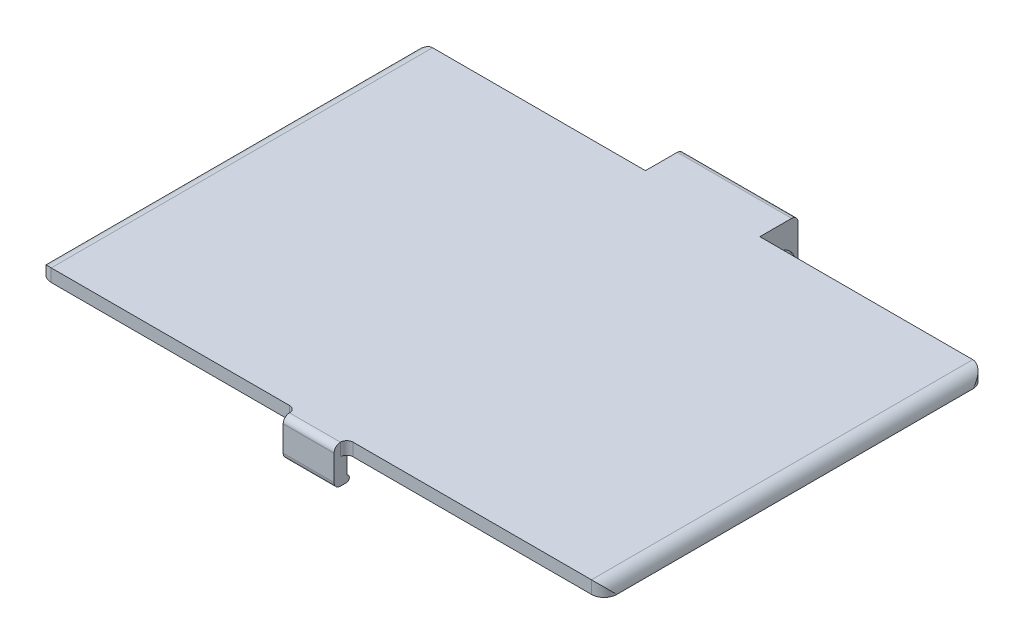
SolidWorks part; units mm, degrees
ref_plane "Přední rovina" through (0, 0, 0) normal (0, 0, 1) x (1, 0, 0)
ref_plane "Horní rovina" through (0, 0, 0) normal (0, 1, 0) x (1, 0, 0)
ref_plane "Pravá rovina" through (0, 0, 0) normal (1, 0, 0) x (0, 0, -1)
sketch "Sketch1" plane through (0, 0, 0) normal (0, 1, 0) x (1, 0, 0)
  line L0 (0, 30) -> (89, 30) construction
  line L1 (0, 0) -> (89, 0)
  line L2 (0, 0) -> (0, 60)
  line L3 (0, 60) -> (89, 60)
  line L4 (89, 0) -> (89, 60)
  line L5 (40.5, 0) -> (48.5, 0)
  line L6 (40.5, 0) -> (40.5, -1)
  line L7 (40.5, -1) -> (48.5, -1)
  line L8 (48.5, 0) -> (48.5, -1)
  line L9 (40.5, 61) -> (48.5, 61)
  line L10 (48.5, 60) -> (48.5, 61)
  line L11 (40.5, 60) -> (48.5, 60)
  line L12 (40.5, 60) -> (40.5, 61)
  point P9 (44.5, 0)
  point P10 (44.5, 0)
  dimension "D1" = 60
  dimension "D2" = 89
  dimension "D3" = 1
  dimension "D4" = 8
extrude "Boss-Extrude1" add sketch "Sketch1" along normal blind 2 contours L2 L0 L4 L3 | L0 L2 L1 L4 | L2 L1 L4 L3 region at (44.5, 0, -45) region at (44.5, 0, -15)
fillet "Fillet6" radius 2 4 edges at (0, 1, 0) (0, 1, -60) (89, 1, -60) (89, 1, 0)
fillet "Fillet8" radius 2 2 edges at (89, 2, -30) (0, 2, -30) tangent propagation no
sketch "Sketch3" plane through (0, 0, -60) normal (0, 0, -1) x (-1, 0, 0)
  line L0 (-44.5, 2) -> (-44.5, 0) construction
  line L1 (-2, 2) -> (-87, 2) construction
  line L2 (-2, 0) -> (-87, 0) construction
  line L4 (-53.5, 2) -> (-35.5, 2)
  line L5 (-53.5, 2) -> (-53.5, -8)
  line L6 (-53.5, -8) -> (-35.5, -8)
  line L7 (-35.5, 2) -> (-35.5, -8)
  line L8 (-51.5, -8) -> (-37.5, -8)
  line L9 (-51.5, -8) -> (-51.5, 0)
  line L10 (-51.5, 0) -> (-37.5, 0)
  line L11 (-37.5, -8) -> (-37.5, 0)
  point P10 (-44.5, 2)
  point P16 (-44.5, 0)
  line M10 (-87, 0) -> (-2, 0)
  line M12 (-2, 2) -> (-87, 2)
  dimension "D1" = 8
  dimension "D2" = 18
  dimension "D3" = 2
extrude "Boss-Extrude2" add sketch "Sketch3" along normal blind 6 contours L6 L9 L5 M10 | L0 L4 L5 M10 | L0 L10 L7 M12 M10 | L11 L6 L7 M10 region at (40, 1, -60) region at (49, 1, -60) region at (52.5, -4, -60) region at (36.5, -4, -60)
ref_plane "Plane2" through (0, 0, -63) normal (0, 0, 1) x (1, 0, 0)
sketch "Sketch9" plane through (0, 0, -63) normal (0, 0, -1) x (-1, 0, 0)
  line L1 (-35.5, 2) -> (-35.5, -8) construction
  line L2 (-2, 0) -> (-35.5, 0) construction
  line L3 (-35.5, -4) -> (-34.3, -4)
  line L4 (-35.5, -1.6) -> (-35.5, -4)
  ellipse E0 centre (-35.5, -4) end of major axis (-35.5, -6.4) minor radius 1.2 (-35.5, -1.6) -> (-34.3, -4) cw
  dimension "D1" = 4
  dimension "D2" = 1.2
  dimension "D3" = 2.4
revolve "Revolve1" add sketch "Sketch9" angle 360 about L3
ref_plane "Plane1" through (44.5, 0, 0) normal (-1, 0, 0) x (0, 0, 1)
mirror "Mirror1" about plane through (44.5, 0, 0) normal (-1, 0, 0) of "Revolve1"
sketch "Sketch5" plane through (0, 0, 0) normal (0, 0, 1) x (1, 0, 0)
  line L0 (44.5, 2) -> (44.5, 0) construction
  line L1 (2, 2) -> (87, 2) construction
  line L2 (2, 0) -> (87, 0) construction
  line L4 (40.5, 2) -> (48.5, 2)
  line L5 (40.5, 2) -> (40.5, -4)
  line L6 (40.5, -4) -> (48.5, -4)
  line L7 (48.5, 2) -> (48.5, -4)
  point P10 (44.5, 2)
  dimension "D1" = 8
  dimension "D2" = 6
extrude "Boss-Extrude3" add sketch "Sketch5" along normal blind 2
fillet "Fillet19" radius 1 4 edges at (44.5, 2, 2) (40.5, 1, 0) (48.5, 1, 0) (44.5, -4, 2)
fillet "Fillet20" radius 3 4 edges at (52.5, -8, -60) (52.5, -8, -66) (36.5, -8, -60) (36.5, -8, -66)
sketch "Sketch8" plane through (40.5, 0, 0) normal (-1, 0, 0) x (0, 0, 1)
  line L0 (0, 0) -> (0, -4) construction
  line L1 (1, -4) -> (0, -4) construction
  line L2 (0, -3) -> (0, -4)
  arc A0 (0, -4) -> (0, -3) centre (0.1, -3.5) cw
  dimension "D1" = 0.1
  dimension "D2" = 1
extrude "Boss-Extrude4" add sketch "Sketch8" against normal up to surface (8 mm away) up to face at (48.5, -1.1429, 1.0592)
fillet "Fillet21" radius 1 1 edges at (44.5, 2, -66)
